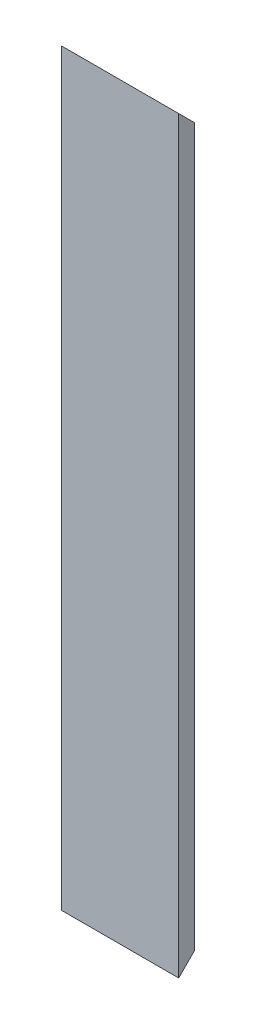
SolidWorks part; units mm, degrees
ref_plane "Front Plane" through (0, 0, 0) normal (0, 0, 1) x (1, 0, 0)
ref_plane "Top Plane" through (0, 0, 0) normal (0, 1, 0) x (1, 0, 0)
ref_plane "Right Plane" through (0, 0, 0) normal (1, 0, 0) x (0, 0, -1)
sketch "Sketch1" plane through (0, 0, 0) normal (0, 1, 0) x (1, 0, 0)
  line L1 (-7.5, 1) -> (7.5, 1)
  line L2 (-7.5, 1) -> (-7.5, -1)
  line L3 (-7.5, -1) -> (7.5, -1)
  line L4 (7.5, 1) -> (7.5, -1)
  point P4 (0, -1)
  point P5 (7.5, 0)
  dimension "D1" = 15
  dimension "D2" = 2
extrude "Boss-Extrude1" add sketch "Sketch1" along normal blind 96
chamfer "Chamfer1" distance 2 angle 45 2 edges at (0, 0, -1) (0, 96, -1)
